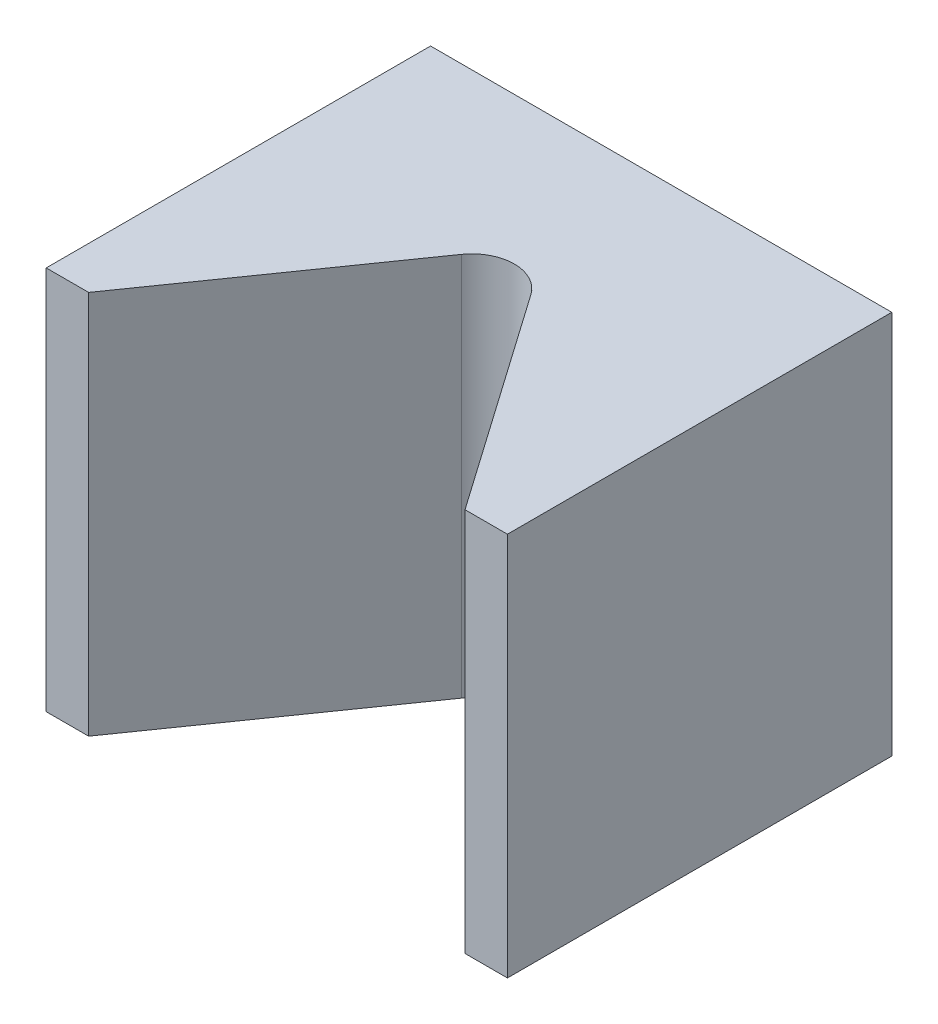
SolidWorks part; units mm, degrees
ref_plane "Front Plane" through (0, 0, 0) normal (0, 0, 1) x (1, 0, 0)
ref_plane "Top Plane" through (0, 0, 0) normal (0, 1, 0) x (1, 0, 0)
ref_plane "Right Plane" through (0, 0, 0) normal (1, 0, 0) x (0, 0, -1)
sketch "Sketch1" plane through (0, 0, 0) normal (0, 1, 0) x (1, 0, 0)
  line L0 (0.9046, 0.6327) -> (4.896, -5.0739)
  line L1 (4.896, -5.0739) -> (6, -5.0739)
  line L2 (6, -5.0739) -> (6, 4.9261)
  line L3 (6, 4.9261) -> (-6, 4.9261)
  line L4 (-6, 4.9261) -> (-6, -5.0739)
  line L5 (-6, -5.0739) -> (-4.896, -5.0739)
  line L6 (-4.896, -5.0739) -> (-0.9046, 0.6327)
  arc A0 (0.9046, 0.6327) -> (-0.9046, 0.6327) centre (0, 0) ccw
  dimension "D4" = 1.104
  dimension "D1" = 10
  dimension "D2" = 10
  dimension "D3" = 12
  dimension "D5" = 6.9639
  dimension "D6" = 6.9639
  dimension "D7" = 1.104
  dimension "D8" = 1.104
  dimension "D9" = 1.8093
  dimension "D10" = 55.03
extrude "Boss-Extrude1" add sketch "Sketch1" along normal blind 10
sketch "Sketch2" plane through (0, 0, -4.9261) normal (0, 0, -1) x (-1, 0, 0)
  line L0 (0, 0) -> (0, 10)
  line L1 (-6, 10) -> (6, 10) construction
  circle A0 centre (0, 5) radius 2.1
  dimension "D1" = 4.2
extrude "Cut-Extrude1" cut sketch "Sketch2" against normal blind 2 contours L0 A0 | L0 A0 region at (0.8913, 5, -4.9261) region at (-0.8913, 5, -4.9261)
